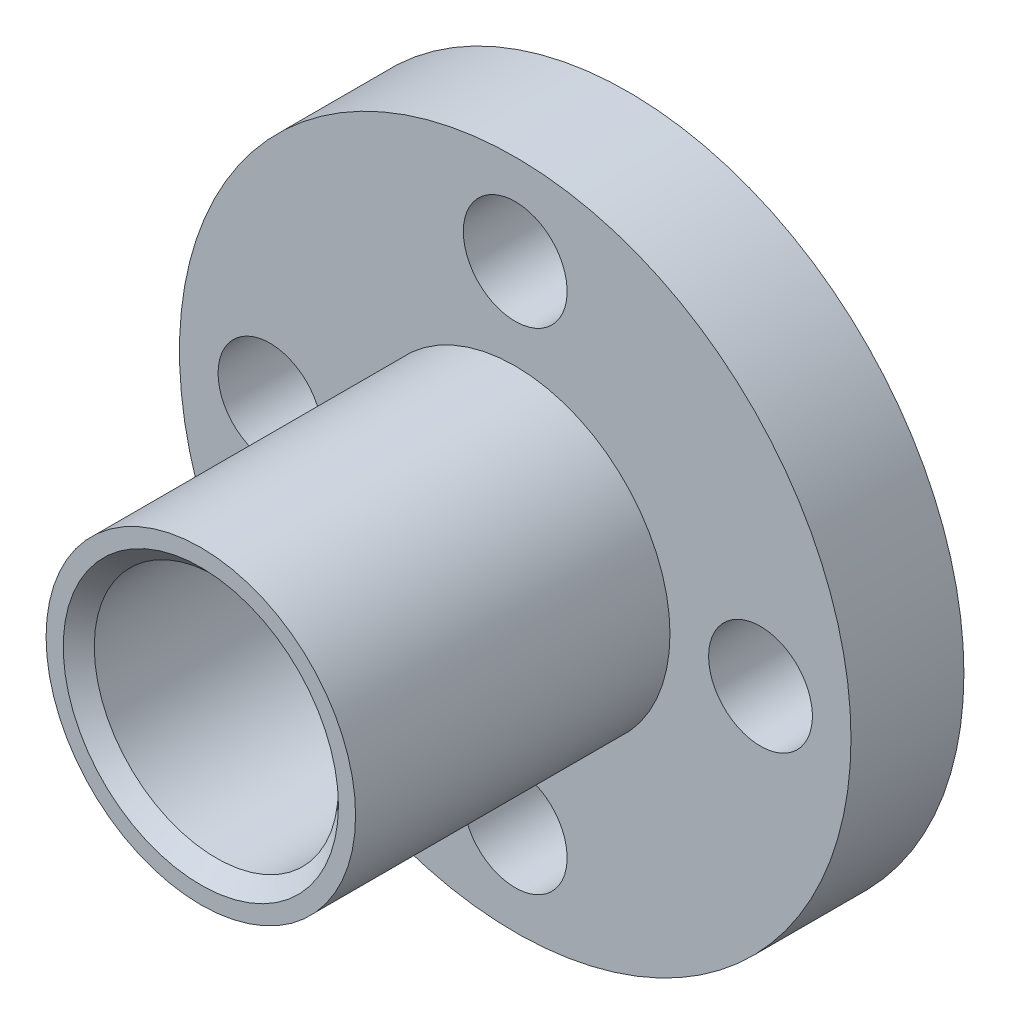
SolidWorks part; units mm, degrees
ref_plane "Front Plane" through (0, 0, 0) normal (0, 0, 1) x (1, 0, 0)
ref_plane "Top Plane" through (0, 0, 0) normal (0, 1, 0) x (1, 0, 0)
ref_plane "Right Plane" through (0, 0, 0) normal (1, 0, 0) x (0, 0, -1)
sketch "Sketch1" plane through (0, 0, 0) normal (0, 0, 1) x (1, 0, 0)
  circle A0 centre (0, 0) radius 11
  circle A1 centre (0, 0) radius 5.07
  circle A2 centre (0, 0) radius 4
extrude "Boss-Extrude1" add sketch "Sketch1" along normal blind 10.3 contours A1 A2 region at (-4.9266, 0, 0)
extrude "Boss-Extrude2" add sketch "Sketch1<3>" against normal blind 3.7 contours A0 A1 | A1 A2 region at (-10.6889, 0, 0) region at (-4.9266, 0, 0)
sketch "Sketch1<3>" plane through (0, 0, 0) normal (0, 0, 1) x (1, 0, 0) same geometry as "Sketch1"
sketch "Sketch2" plane through (0, 0, -3.7) normal (0, 0, -1) x (-1, 0, 0)
  circle A0 centre (0, 0) radius 5.07 construction
  circle A1 centre (0, 0) radius 4 construction
  circle A2 centre (0, 0) radius 5.07
  circle A3 centre (0, 0) radius 4
extrude "Boss-Extrude3" add sketch "Sketch2" along normal blind 1.5
chamfer "Chamfer1" distance 0.508 angle 45 2 edges at (-4, 0, -5.2) (4, 0, 10.3)
sketch "Sketch3" plane through (0, 0, -3.7) normal (0, 0, -1) x (-1, 0, 0)
  line L0 (-5.07, 0) -> (-11, 0)
  circle A0 centre (0, 0) radius 11 construction
  circle A1 centre (0, 0) radius 11
  circle A2 centre (0, 0) radius 5.07 construction
  circle A3 centre (0, 0) radius 5.07
  circle A4 centre (0, 0) radius 4.508 construction
  circle A5 centre (0, 0) radius 4.508
  circle A6 centre (0, 0) radius 4 construction
  circle A7 centre (0, 0) radius 4
  circle A8 centre (-8.035, 0) radius 1.7
  circle A9 centre (0, 8.035) radius 1.7
  circle A10 centre (8.035, 0) radius 1.7
  circle A11 centre (0, -8.035) radius 1.7
  point P22 (0, 0)
  dimension "D1" = 4
extrude "Cut-Extrude1" cut sketch "Sketch3" against normal blind 4.294 contours A8 | A9 | A10 | A11
